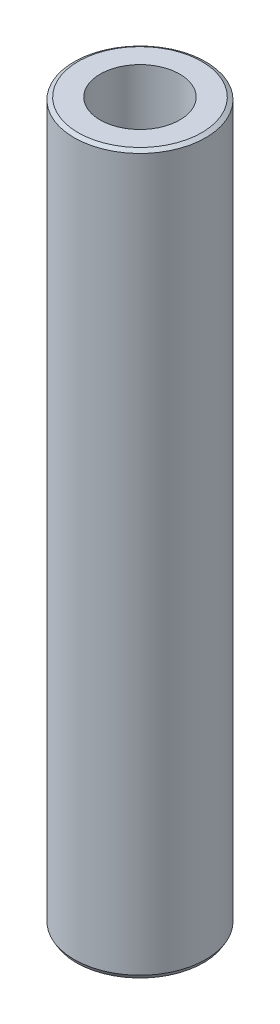
SolidWorks part; units mm, degrees
ref_plane "Front Plane" through (0, 0, 0) normal (0, 0, 1) x (1, 0, 0)
ref_plane "Top Plane" through (0, 0, 0) normal (0, 1, 0) x (1, 0, 0)
ref_plane "Right Plane" through (0, 0, 0) normal (1, 0, 0) x (0, 0, -1)
sketch "Sketch1" plane through (0, 0, 0) normal (0, 1, 0) x (1, 0, 0)
  circle A0 centre (0, 0) radius 55
  dimension "SHAFT_OD" = 110
extrude "Boss-Extrude1" add sketch "Sketch1" along normal blind 600
sketch "Sketch2" plane through (0, 0, 0) normal (0, 1, 0) x (1, 0, 0)
  circle A0 centre (0, 0) radius 33.2494
  dimension "BORE_D" = 66.4987
extrude "Cut-Extrude1" cut sketch "Sketch2" along normal through all
chamfer "Chamfer1" distance 1.9521 angle 60 2 edges at (0, 600, 55) (0, 0, 55) first distance on face at (0, 600, 55) first distance on face at (0, 0, 33.2494)
